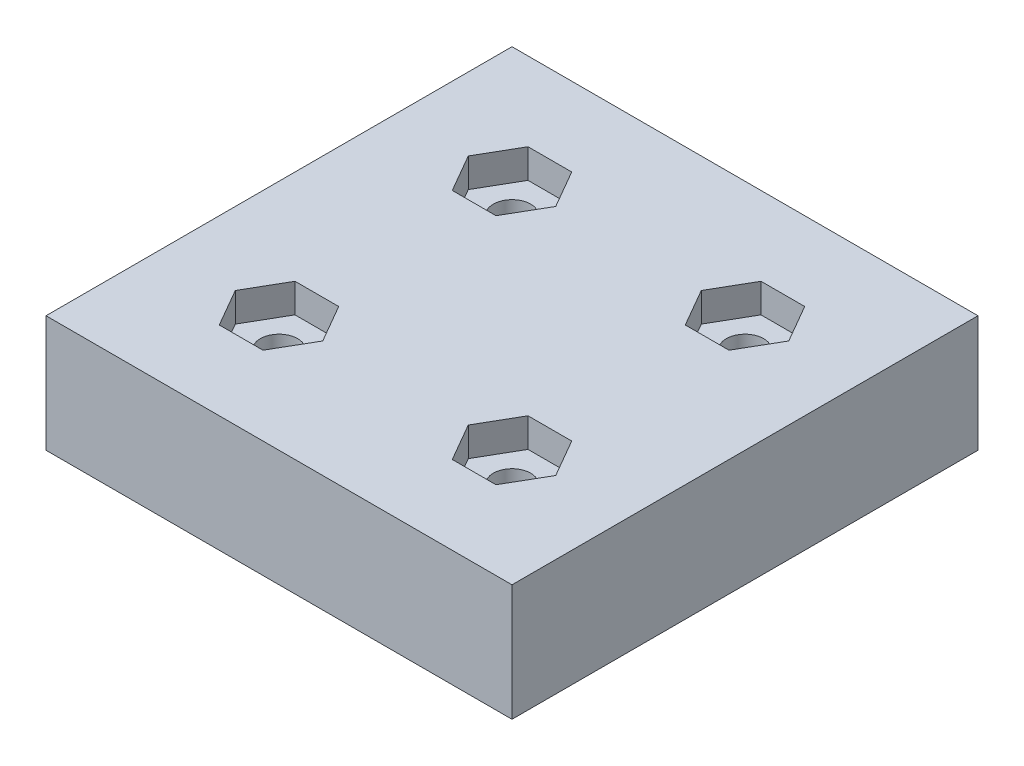
SolidWorks part; units mm, degrees
ref_plane "Front Plane" through (0, 0, 0) normal (0, 0, 1) x (1, 0, 0)
ref_plane "Top Plane" through (0, 0, 0) normal (0, 1, 0) x (1, 0, 0)
ref_plane "Right Plane" through (0, 0, 0) normal (1, 0, 0) x (0, 0, -1)
sketch "Sketch1" plane through (0, 0, 0) normal (0, 1, 0) x (1, 0, 0)
  line L1 (0, 0) -> (40, 0)
  line L2 (0, 0) -> (0, 40)
  line L3 (0, 40) -> (40, 40)
  line L4 (40, 0) -> (40, 40)
  circle A0 centre (10, 30) radius 1.6
  circle A1 centre (30, 30) radius 1.6
  circle A2 centre (30, 10) radius 1.6
  circle A3 centre (10, 10) radius 1.6
  dimension "D11" = 3.2
  dimension "D12" = 3.2
  dimension "D13" = 3.2
  dimension "D14" = 3.2
  dimension "D1" = 40
  dimension "D2" = 40
  dimension "D3" = 10
  dimension "D4" = 10
  dimension "D5" = 10
  dimension "D6" = 10
  dimension "D7" = 10
  dimension "D8" = 10
  dimension "D9" = 10
  dimension "D10" = 10
extrude "Boss-Extrude1" add sketch "Sketch1" along normal blind 10
sketch "Sketch2" plane through (0, 10, 0) normal (0, 1, 0) x (1, 0, 0)
  line L0 (10, 10) -> (30, 10) construction
  line L1 (30, 10) -> (30, 30) construction
  line L2 (30, 30) -> (10, 30) construction
  line L3 (10, 30) -> (10, 10) construction
  line L5 (13.7528, 10) -> (11.8764, 13.25)
  line L6 (11.8764, 13.25) -> (8.1236, 13.25)
  line L7 (8.1236, 13.25) -> (6.2472, 10)
  line L8 (6.2472, 10) -> (8.1236, 6.75)
  line L9 (8.1236, 6.75) -> (11.8764, 6.75)
  line L10 (11.8764, 6.75) -> (13.7528, 10)
  line L11 (26.2472, 10) -> (28.1236, 6.75)
  line L12 (28.1236, 6.75) -> (31.8764, 6.75)
  line L13 (31.8764, 6.75) -> (33.7528, 10)
  line L14 (33.7528, 10) -> (31.8764, 13.25)
  line L15 (31.8764, 13.25) -> (28.1236, 13.25)
  line L16 (28.1236, 13.25) -> (26.2472, 10)
  line L17 (26.2472, 30) -> (28.1236, 26.75)
  line L18 (28.1236, 26.75) -> (31.8764, 26.75)
  line L19 (31.8764, 26.75) -> (33.7528, 30)
  line L20 (33.7528, 30) -> (31.8764, 33.25)
  line L21 (31.8764, 33.25) -> (28.1236, 33.25)
  line L22 (28.1236, 33.25) -> (26.2472, 30)
  line L23 (13.7528, 30) -> (11.8764, 33.25)
  line L24 (11.8764, 33.25) -> (8.1236, 33.25)
  line L25 (8.1236, 33.25) -> (6.2472, 30)
  line L26 (6.2472, 30) -> (8.1236, 26.75)
  line L27 (8.1236, 26.75) -> (11.8764, 26.75)
  line L28 (11.8764, 26.75) -> (13.7528, 30)
  circle A0 centre (10, 10) radius 3.25 construction
  circle A1 centre (30, 10) radius 3.25 construction
  circle A2 centre (30, 30) radius 3.25 construction
  circle A3 centre (10, 30) radius 3.25 construction
  dimension "D1" = 6.5
  dimension "D2" = 6.5
  dimension "D3" = 6.5
  dimension "D4" = 6.5
extrude "Cut-Extrude1" cut sketch "Sketch2" against normal blind 2.5
equation "\"hSpacing\"=10"
equation "\"D3@Sketch1\"=\"hSpacing\""
equation "\"D5@Sketch1\"=\"hSpacing\""
equation "\"D6@Sketch1\"=\"hSpacing\""
equation "\"D4@Sketch1\"=\"hSpacing\""
equation "\"D7@Sketch1\"=\"hSpacing\""
equation "\"D8@Sketch1\"=\"hSpacing\""
equation "\"D9@Sketch1\"=\"hSpacing\""
equation "\"D10@Sketch1\"=\"hSpacing\""
equation "\"hDiam\"=3.2"
equation "\"D11@Sketch1\"=\"hDiam\""
equation "\"D12@Sketch1\"=\"hDiam\""
equation "\"D13@Sketch1\"=\"hDiam\""
equation "\"D14@Sketch1\"=\"hDiam\""
equation "\"nutFlat\"=6.5"
equation "\"D1@Sketch2\"=\"nutFlat\""
equation "\"D2@Sketch2\"=\"nutFlat\""
equation "\"D3@Sketch2\"=\"nutFlat\""
equation "\"D4@Sketch2\"=\"nutFlat\""
